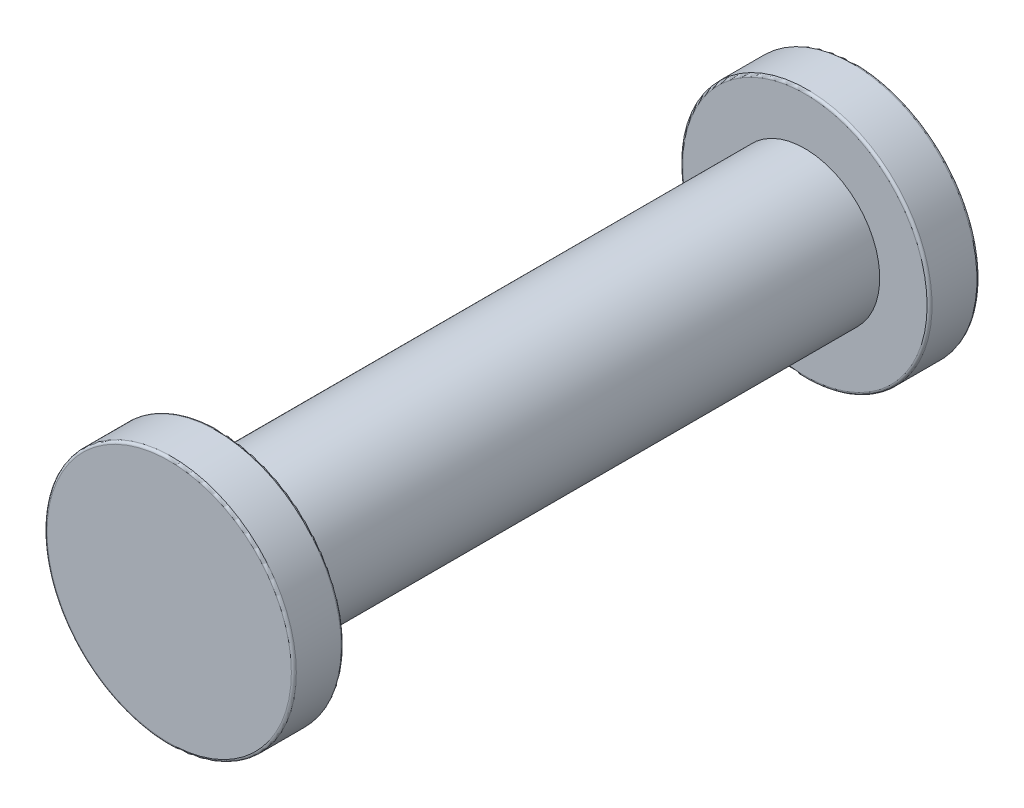
SolidWorks part; units mm, degrees
ref_plane "Front Plane" through (0, 0, 0) normal (0, 0, 1) x (1, 0, 0)
ref_plane "Top Plane" through (0, 0, 0) normal (0, 1, 0) x (1, 0, 0)
ref_plane "Right Plane" through (0, 0, 0) normal (1, 0, 0) x (0, 0, -1)
sketch "Sketch1" plane through (0, 0, 0) normal (0, 0, 1) x (1, 0, 0)
  circle A1 centre (0, 0) radius 2.5
  dimension "D2" = 5
extrude "Boss-Extrude1" add sketch "Sketch1" against normal blind 1 contours A1
sketch "Sketch2" plane through (0, 0, -1) normal (0, 0, -1) x (-1, 0, 0)
  circle A0 centre (0, 0) radius 1.5
  dimension "D1" = 3
extrude "Boss-Extrude2" add sketch "Sketch2" along normal blind 11.75
extrude "Boss-Extrude3" add sketch "Sketch1<5>" against normal blind 1 from surface starting at face at (-1.5, 0, -12.75)
sketch "Sketch1<5>" plane through (0, 0, 0) normal (0, 0, 1) x (1, 0, 0) same geometry as "Sketch1"
fillet "Fillet1" radius 0.05 4 edges at (2.5, 0, -1) (-2.5, 0, -12.75) (2.5, 0, 0) (-2.5, 0, -13.75)
scale "Scale1" scale about centroid uniform scaling yes scale factor 1.9
